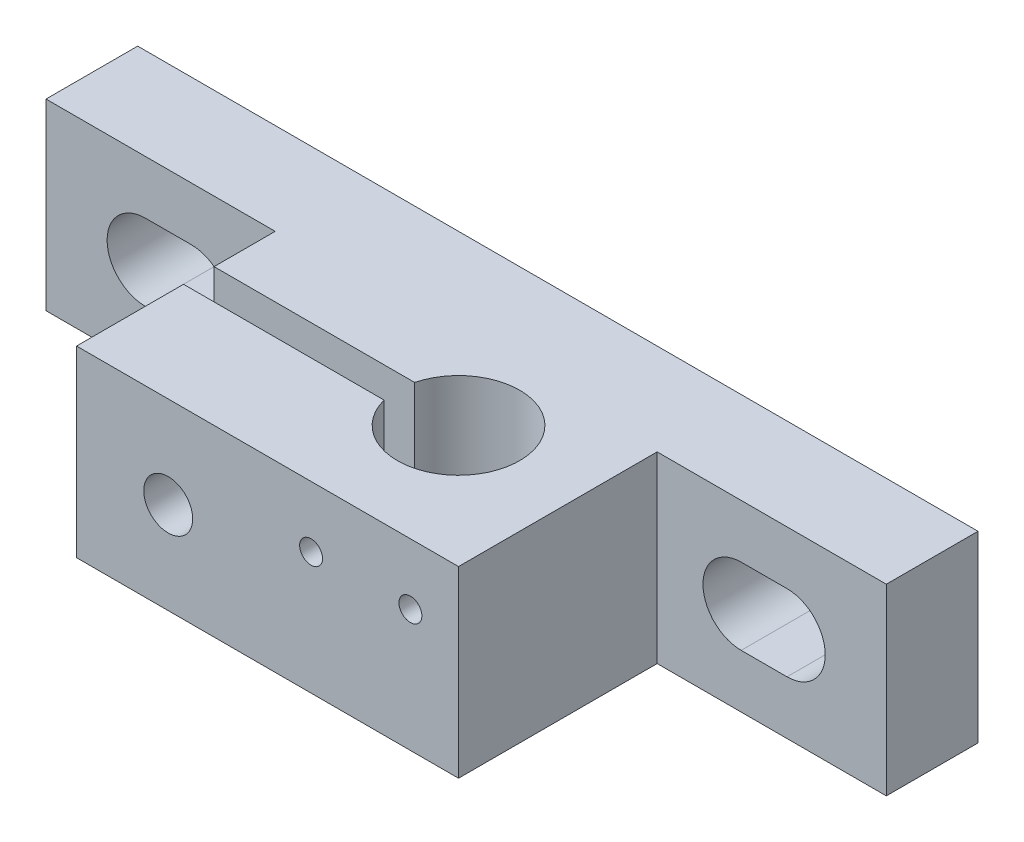
SolidWorks part; units mm, degrees
material "Copper"
ref_plane "Front Plane" through (0, 0, 0) normal (0, 0, 1) x (1, 0, 0)
ref_plane "Top Plane" through (0, 0, 0) normal (0, 1, 0) x (1, 0, 0)
ref_plane "Right Plane" through (0, 0, 0) normal (1, 0, 0) x (0, 0, -1)
sketch "Sketch2" plane through (0, 0, 0) normal (0, 0, 1) x (1, 0, 0)
  line L0 (6.5, 6) -> (9.5, 6) construction
  line L1 (0, 0) -> (55, 0)
  line L2 (0, 0) -> (0, 12)
  line L3 (0, 12) -> (55, 12)
  line L4 (55, 0) -> (55, 12)
  line L5 (27.5, 12) -> (27.5, -3.75) construction
  line L6 (6.5, 8.5) -> (9.5, 8.5)
  line L7 (6.5, 3.5) -> (9.5, 3.5)
  line L8 (48.5, 6) -> (45.5, 6) construction
  line L9 (48.5, 8.5) -> (45.5, 8.5)
  line L10 (48.5, 3.5) -> (45.5, 3.5)
  arc A0 (6.5, 8.5) -> (6.5, 3.5) centre (6.5, 6) ccw
  arc A1 (48.5, 8.5) -> (48.5, 3.5) centre (48.5, 6) cw
  arc A2 (9.5, 3.5) -> (9.5, 8.5) centre (9.5, 6) ccw
  arc A3 (45.5, 3.5) -> (45.5, 8.5) centre (45.5, 6) cw
  point P11 (8, 6)
  point P16 (47, 6)
  dimension "D1" = 6.5
  dimension "D2" = 3
  dimension "D5" = 55
extrude "Boss-Extrude1" add sketch "Sketch2" along normal blind 6
sketch "Sketch3" plane through (0, 0, 6) normal (0, 0, 1) x (1, 0, 0)
  line L0 (0, 0) -> (55, 0) construction
  line L1 (15, 0) -> (40, 0)
  line L2 (15, 0) -> (15, 12)
  line L3 (15, 12) -> (40, 12)
  line L4 (40, 0) -> (40, 12)
  line L5 (55, 12) -> (0, 12) construction
  line L6 (0, 12) -> (0, 0) construction
  line L7 (55, 0) -> (55, 12) construction
  dimension "D1" = 25
  dimension "D2" = 15
  dimension "D3" = 15
extrude "Boss-Extrude2" add sketch "Sketch3" along normal blind 13
sketch "Sketch4" plane through (0, 0, 0) normal (0, -1, 0) x (1, 0, 0)
  line L0 (15, 19) -> (40, 19) construction
  line L1 (40, 19) -> (40, 6) construction
  line L2 (0, 0) -> (55, 0) construction
  line L3 (28.127, 12) -> (15, 12)
  line L4 (15, 19) -> (15, 6) construction
  line L5 (15, 12) -> (15, 10)
  line L6 (15, 10) -> (28.127, 10)
  circle A0 centre (32, 11) radius 4
  line M4 (15, 19) -> (15, 6)
  dimension "D1" = 8
  dimension "D5" = 8
  dimension "D7" = 11
  dimension "D2" = 8
  dimension "D3" = 11
  dimension "D4" = 1
  dimension "D6" = 1
extrude "Cut-Extrude2" cut sketch "Sketch4" against normal blind 30 contours A0 L3 L6 M4 | A0 region at (21.5211, 0, 11) region at (32, 0, 11)
sketch "Sketch5" plane through (0, 0, 0) normal (0, 0, -1) x (-1, 0, 0)
  line L0 (-55, 12) -> (0, 12) construction
  line L1 (-37.6724, 9.5) -> (-17.1585, 9.5)
  line L2 (-37.6724, 9.5) -> (-37.6724, 2.5)
  line L3 (-37.6724, 2.5) -> (-17.1585, 2.5)
  line L4 (-17.1585, 9.5) -> (-17.1585, 2.5)
  line L5 (0, 0) -> (-55, 0) construction
  line L6 (0, 12) -> (0, 0) construction
  dimension "D1" = 20.5139
  dimension "D2" = 2.5
  dimension "D3" = 2.5
  dimension "D4" = 17.1585
extrude "Cut-Extrude3" cut sketch "Sketch5" against normal blind 5
sketch "Sketch6" plane through (0, 0, 19) normal (0, 0, 1) x (1, 0, 0)
  line L0 (15, 12) -> (15, 0) construction
  line L1 (40, 12) -> (15, 12) construction
  line L2 (15, 0) -> (40, 0) construction
  circle A0 centre (21, 6) radius 1.6
  dimension "D1" = 6
  dimension "D2" = 6
  dimension "D3" = 6
extrude "Cut-Extrude4" cut sketch "Sketch6" against normal blind 20
sketch "Sketch7" plane through (0, 0, 5) normal (0, 0, -1) x (-1, 0, 0)
  line L1 (-17.5359, 6) -> (-19.2679, 9)
  line L2 (-19.2679, 9) -> (-22.7321, 9)
  line L3 (-22.7321, 9) -> (-24.4641, 6)
  line L4 (-24.4641, 6) -> (-22.7321, 3)
  line L5 (-22.7321, 3) -> (-19.2679, 3)
  line L6 (-19.2679, 3) -> (-17.5359, 6)
  circle A0 centre (-21, 6) radius 3 construction
extrude "Cut-Extrude5" cut sketch "Sketch7" against normal blind 3
sketch "Sketch8" plane through (0, 0, 19) normal (0, 0, 1) x (1, 0, 0)
  line L0 (40, 0) -> (40, 12) construction
  line L1 (40, 12) -> (15, 12) construction
  circle A0 centre (36.85, 8) radius 0.75
  circle A1 centre (30.35, 8) radius 0.75
  dimension "D1" = 1.5
  dimension "D2" = 3.15
  dimension "D3" = 4
  dimension "D4" = 2
extrude "Cut-Extrude6" cut sketch "Sketch8" against normal blind 3
